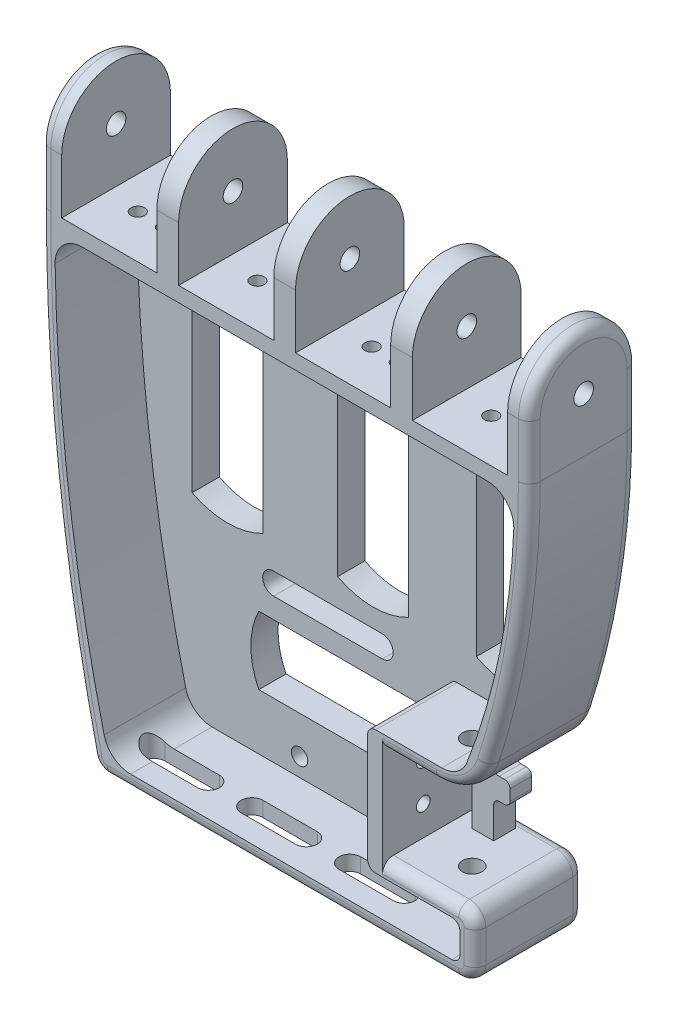
SolidWorks part; units mm, degrees
note: The reader was unsure of these and kept them because the rebuilt part matched: shared geometry of "Sketch4<4>".
ref_plane "Front Plane" through (0, 0, 0) normal (0, 0, 1) x (1, 0, 0)
ref_plane "Top Plane" through (0, 0, 0) normal (0, 1, 0) x (1, 0, 0)
ref_plane "Right Plane" through (0, 0, 0) normal (1, 0, 0) x (0, 0, -1)
sketch "Sketch1" plane through (0, 0, 0) normal (0, 0, 1) x (1, 0, 0)
  line L0 (0, 0) -> (-70, 0)
  line L1 (10, 85) -> (-80, 85)
  line L2 (0.003, 29.6) -> (-16.997, 29.6)
  line L3 (-16.997, 29.6) -> (-16.997, 12)
  line L5 (-16.997, 12) -> (0, 12)
  line L6 (0, 12) -> (0, 0)
  arc A0 (-80, 85) -> (-70, 0) centre (286.25, 85) ccw
  arc A1 (10, 85) -> (0.003, 29.6) centre (-148.5029, 85) cw
  point P5 (-35, 85)
  point P6 (-35, 0)
  dimension "D5" = 17.6
  dimension "D6" = 12
  dimension "D7" = 16.997
  dimension "D4" = 17
  dimension "D1" = 90
  dimension "D2" = 70
  dimension "D3" = 85
extrude "Boss-Extrude1" add sketch "Sketch1" along normal blind 20
sketch "Sketch2" plane through (0, 0, 20) normal (0, 0, 1) x (1, 0, 0)
  line L0 (-77.25, 82.25) -> (7.25, 82.25)
  line L1 (-2.7437, 32.35) -> (-19.7437, 32.35)
  line L2 (-19.7437, 32.35) -> (-19.7437, 9.5)
  line L3 (-19.7437, 9.5) -> (-2.75, 9.5)
  line L4 (-2.75, 9.5) -> (-2.75, 2.75)
  line L5 (-2.75, 2.75) -> (-67.25, 2.75)
  line L6 (0, 12) -> (-16.997, 12) construction
  arc A0 (7.25, 82.25) -> (-2.7437, 32.35) centre (-122.326, 82.25) cw
  arc A1 (-77.25, 82.25) -> (-67.25, 2.75) centre (243.7625, 82.25) ccw
  arc A2 (-72.2104, 82.25) -> (-77.2098, 77.1709) centre (-72.2104, 77.25) ccw
  arc A3 (7.1456, 77.0493) -> (2.1496, 82.25) centre (2.1496, 77.25) ccw
  arc A4 (-6.1229, 32.35) -> (-1.4589, 35.5479) centre (-6.1229, 37.35) ccw
  arc A5 (-68.2018, 6.5712) -> (-63.3428, 2.75) centre (-63.3428, 7.75) ccw
  arc A6 (-2.75, 8) -> (-4.25, 9.5) centre (-4.25, 8) ccw
  arc A7 (-4.25, 2.75) -> (-2.75, 4.25) centre (-4.25, 4.25) ccw
  arc A8 (-19.7437, 11) -> (-18.2437, 9.5) centre (-18.2437, 11) ccw
  arc A9 (-18.2437, 32.35) -> (-19.7437, 30.85) centre (-18.2437, 30.85) ccw
  point P10 (-35, 82.25)
  point P11 (-35, 2.75)
  dimension "D7" = 2.75
  dimension "D9" = 10
  dimension "D11" = 3
  dimension "D12" = 3
  dimension "D13" = 3
  dimension "D1" = 2.75
  dimension "D2" = 2.75
  dimension "D3" = 2.7467
  dimension "D4" = 2.7467
  dimension "D5" = 2.75
  dimension "D6" = 2.75
  dimension "D8" = 2.75
  dimension "D10" = 2.5
extrude "Cut-Extrude1" cut sketch "Sketch2" against normal blind 15 contours L5 A7 L4 A6 L3 L2 L1 A4 A0 A3 L0 A2 A1 A5 | A9 L1 L2 | A8 L2 L3
sketch "Sketch3" plane through (0, 85, 0) normal (0, 1, 0) x (1, 0, 0)
  line L0 (10, -20) -> (-80, -20) construction
  line L1 (-80, 0) -> (-76, 0)
  line L2 (-80, 0) -> (-80, -20)
  line L3 (-80, -20) -> (-76, -20)
  line L4 (-76, 0) -> (-76, -20)
  line L5 (-58.5, -20) -> (-54.5, -20)
  line L6 (-58.5, -20) -> (-58.5, 0)
  line L7 (-58.5, 0) -> (-54.5, 0)
  line L8 (-54.5, -20) -> (-54.5, 0)
  line L9 (10, 0) -> (-80, 0) construction
  line L10 (10, -20) -> (10, 0) construction
  line L11 (-37, 0) -> (-33, 0)
  line L12 (-37, -20) -> (-33, -20)
  line L13 (-37, 0) -> (-37, -20)
  line L15 (-15.5, 0) -> (-11.5, 0)
  line L16 (-15.5, 0) -> (-15.5, -20)
  line L17 (-15.5, -20) -> (-11.5, -20)
  line L18 (-11.5, 0) -> (-11.5, -20)
  line L19 (6, 0) -> (10, 0)
  line L20 (6, 0) -> (6, -20)
  line L21 (6, -20) -> (10, -20)
  line L22 (10, 0) -> (10, -20)
  line L23 (-33, 0) -> (-33, -20)
  point P27 (-58.5, -10)
  dimension "D1" = 4
  dimension "D2" = 4
  dimension "D3" = 4
  dimension "D4" = 4
  dimension "D5" = 4
  dimension "D6" = 17.5
  dimension "D7" = 17.5
  dimension "D8" = 17.5
extrude "Boss-Extrude2" add sketch "Sketch3" along normal blind 20
sketch "Sketch4" plane through (-80, 0, 0) normal (-1, 0, 0) x (0, 0, 1)
  line L0 (0, 85) -> (0, 105)
  line L1 (0, 105) -> (20, 105)
  line L2 (0, 85) -> (20, 85)
  line L3 (0, 95) -> (8.2, 95)
  line L4 (11.8, 95) -> (20, 95)
  line L5 (20, 105) -> (20, 85)
  arc A0 (0, 95) -> (20, 95) centre (10, 95) cw
  circle A1 centre (10, 95) radius 1.8
  point P3 (0, 95)
  point P5 (10, 105)
  dimension "D1" = 3.6
extrude "Cut-Extrude2" cut sketch "Sketch4" against normal through all
extrude "Cut-Extrude3" cut sketch "Sketch4<4>" against normal through all contours A1
sketch "Sketch4<4>" plane through (-80, 0, 0) normal (-1, 0, 0) x (0, 0, 1) same geometry as "Sketch4"
ref_plane "Plane1" through (0, 85, 0) normal (0, 1, 0) x (1, 0, 0)
sketch "Sketch7" plane through (0, 32.35, 0) normal (0, 1, 0) x (1, 0, 0)
  line L4 (-18.2437, -5) -> (-18.2437, -20) construction
  line L6 (0.003, -20) -> (0.003, 0) construction
  circle A0 centre (-7.997, -12.5) radius 1.8
  point P10 (-18.2437, -12.5)
  dimension "D1" = 3.6
  dimension "D2" = 8
extrude "Cut-Extrude5" cut sketch "Sketch7" against normal blind 25
sketch "Sketch9" plane through (0, 85, 0) normal (0, 1, 0) x (1, 0, 0)
  line L0 (-76, -20) -> (-76, -10) construction
  line L2 (-56.5, 0) -> (-56.5, -50000) construction
  line L3 (-54.5, 0) -> (-58.5, 0) construction
  line L4 (-35, 0) -> (-35, -50000) construction
  line L5 (-33, 0) -> (-37, 0) construction
  line L7 (-58.5, 0) -> (-76, 0) construction
  circle A0 centre (-70, -12) radius 1.25
  circle A1 centre (-65, -12) radius 1.25
  circle A2 centre (-48, -12) radius 1.25
  circle A3 centre (-43, -12) radius 1.25
  circle A4 centre (-27, -12) radius 1.25
  circle A5 centre (-22, -12) radius 1.25
  circle A6 centre (-5, -12) radius 1.25
  circle A7 centre (0, -12) radius 1.25
  point P14 (-56.5, 0)
  point P22 (-35, 0)
  point P34 (-76, -15)
  dimension "D1" = 2.5
  dimension "D2" = 2.5
  dimension "D3" = 12
  dimension "D4" = 6
  dimension "D5" = 5
extrude "Cut-Extrude6" cut sketch "Sketch9" against normal blind 10
sketch "Sketch10" plane through (0, 0, 6) normal (0, 0, 1) x (1, 0, 0)
  line L0 (-35.4209, 73.25) -> (35.4209, 73.25) construction
  line L1 (-32.0539, 38.25) -> (49967.9461, 38.25) construction
  line L2 (2.1496, 82.25) -> (-72.2104, 82.25) construction
  line L4 (-67, 73.25) -> (-54, 73.25)
  line L5 (-67, 73.25) -> (-67, 38.25)
  line L6 (-67, 38.25) -> (-54, 38.25)
  line L7 (-54, 73.25) -> (-54, 38.25)
  line L8 (-40.25, 73.25) -> (-27.25, 73.25)
  line L9 (-40.25, 73.25) -> (-40.25, 38.25)
  line L10 (-40.25, 38.25) -> (-27.25, 38.25)
  line L11 (-27.25, 73.25) -> (-27.25, 38.25)
  line L12 (-14.75, 73.25) -> (-1.75, 73.25)
  line L13 (-14.75, 73.25) -> (-14.75, 38.25)
  line L14 (-14.75, 38.25) -> (-1.75, 38.25)
  line L15 (-1.75, 73.25) -> (-1.75, 38.25)
  line L16 (6, 85) -> (-11.5, 85) construction
  line L19 (-15.5, 85) -> (-33, 85) construction
  arc A0 (-67, 73.25) -> (-54, 73.25) centre (-60.5, 60.8504) cw
  arc A1 (-67, 38.25) -> (-54, 38.25) centre (-60.5, 50.6496) ccw
  arc A2 (-40.25, 73.25) -> (-27.25, 73.25) centre (-33.75, 60.8504) cw
  arc A3 (-40.25, 38.25) -> (-27.25, 38.25) centre (-33.75, 50.6496) ccw
  arc A4 (-14.75, 38.25) -> (-1.75, 38.25) centre (-8.25, 50.6496) ccw
  arc A5 (-14.75, 73.25) -> (-1.75, 73.25) centre (-8.25, 60.8504) cw
  point P6 (0, 73.25)
  point P21 (-2.75, 85)
  point P25 (-24.25, 85)
  dimension "D9" = 14
  dimension "D1" = 9
  dimension "D2" = 35
  dimension "D3" = 13
  dimension "D4" = 13
  dimension "D5" = 13
  dimension "D6" = 12
  dimension "D7" = 16
  dimension "D8" = 13
extrude "Cut-Extrude9" cut sketch "Sketch10" against normal mid plane 43 contours L7 L4 L5 L6 | L11 L8 L9 L10 | L15 L12 L13 L14 | L14 A4 | L10 A3 | L6 A1 | A0 L4 | A2 L8 | A5 L12
sketch "Sketch11" plane through (-19.7437, 0, 0) normal (-1, 0, 0) x (0, 0, 1)
  line L1 (6, 32.35) -> (16, 32.35) construction
  line L2 (5, 30.85) -> (20, 30.85) construction
  circle A0 centre (12.5, 24.455) radius 1.25
  circle A1 centre (12.5, 17.455) radius 1.25
  point P12 (12.5, 30.85)
  dimension "D1" = 2.5
  dimension "D2" = 2.5
  dimension "D3" = 7
  dimension "D4" = 7.895
extrude "Cut-Extrude10" cut sketch "Sketch11" against normal blind 33
sketch "Sketch12" plane through (0, 0, 6) normal (0, 0, 1) x (1, 0, 0)
  line L1 (-54.7437, 25.5) -> (-24.7437, 25.5)
  line L2 (-54.7437, 25.5) -> (-54.7437, 13)
  line L3 (-54.7437, 13) -> (-24.7437, 13)
  line L4 (-24.7437, 25.5) -> (-24.7437, 13)
  line L6 (-19.7437, 9.5573) -> (-19.7437, 32.35) construction
  arc A0 (-54.7437, 25.5) -> (-54.7437, 13) centre (-42.2162, 19.25) ccw
  arc A1 (-24.7437, 25.5) -> (-24.7437, 13) centre (-37.2712, 19.25) cw
  dimension "D5" = 14
  dimension "D6" = 14
  dimension "D1" = 30
  dimension "D2" = 12.5
  dimension "D3" = 5
  dimension "D4" = 13
extrude "Cut-Extrude11" cut sketch "Sketch12" against normal mid plane 63 contours L4 L1 L2 L3 | A1 L4 | L2 A0
sketch "Sketch15" plane through (0, 0, 6) normal (0, 0, 1) x (1, 0, 0)
  line L0 (-68, 73.25) -> (-68, 43.25) construction
  line L1 (-2.75, 4.25) -> (-2.75, 8) construction
  circle A0 centre (-47.25, 6.125) radius 1.5
  circle A1 centre (-19.7437, 6.125) radius 1.5
  circle A2 centre (1.75, 76.125) radius 1.5
  circle A3 centre (-47.25, 76.125) radius 1.5
  point P22 (-2.75, 6.125)
  dimension "D1" = 3
  dimension "D4" = 49
  dimension "D5" = 70
  dimension "D6" = 20.75
extrude "Cut-Extrude13" cut sketch "Sketch15" along normal mid plane 100
sketch "Sketch16" plane through (0, 0, 0) normal (0, -1, 0) x (1, 0, 0)
  line L0 (-37, 14) -> (-47, 14) construction
  line L1 (-37, 12) -> (-47, 12)
  line L2 (-37, 16) -> (-47, 16)
  line L3 (-29, 14) -> (-19, 14) construction
  line L4 (-29, 16) -> (-19, 16)
  line L5 (-29, 12) -> (-19, 12)
  line L6 (-55, 14) -> (-65, 14) construction
  line L7 (-55, 12) -> (-65, 12)
  line L8 (-55, 16) -> (-65, 16)
  line L9 (-70, 20) -> (0, 20) construction
  arc A0 (-37, 12) -> (-37, 16) centre (-37, 14) ccw
  arc A1 (-47, 16) -> (-47, 12) centre (-47, 14) ccw
  arc A2 (-29, 16) -> (-29, 12) centre (-29, 14) ccw
  arc A3 (-19, 12) -> (-19, 16) centre (-19, 14) ccw
  arc A4 (-55, 12) -> (-55, 16) centre (-55, 14) ccw
  arc A5 (-65, 16) -> (-65, 12) centre (-65, 14) ccw
  point P2 (-42, 14)
  point P7 (-24, 14)
  point P14 (-60, 14)
  dimension "D1" = 2
  dimension "D2" = 10
  dimension "D3" = 55
  dimension "D4" = 18
  dimension "D5" = 18
  dimension "D6" = 6
extrude "Cut-Extrude14" cut sketch "Sketch16" against normal blind 7
sketch "Sketch17" plane through (0, 0, 6) normal (0, 0, 1) x (1, 0, 0)
  line L0 (-52.0304, 31.25) -> (-32.0304, 31.25) construction
  line L1 (-52.0304, 33.25) -> (-32.0304, 33.25)
  line L2 (-52.0304, 29.25) -> (-32.0304, 29.25)
  line L3 (2.1496, 82.25) -> (-72.2104, 82.25) construction
  line L4 (7.25, 82.25) -> (-77.25, 82.25) construction
  arc A0 (-52.0304, 33.25) -> (-52.0304, 29.25) centre (-52.0304, 31.25) ccw
  arc A1 (-32.0304, 29.25) -> (-32.0304, 33.25) centre (-32.0304, 31.25) ccw
  arc A2 (-52.0304, 33.25) -> (-50.0304, 31.25) centre (-52.0304, 31.25) ccw
  arc A3 (-34.0304, 31.25) -> (-32.0304, 33.25) centre (-32.0304, 31.25) ccw
  arc A4 (-44.0304, 31.25) -> (-40.0304, 31.25) centre (-42.0304, 31.25) ccw
  point P2 (-42.0304, 31.25)
  point P7 (-30.0304, 31.25)
  point P11 (-35.0304, 82.25)
  dimension "D1" = 20
  dimension "D2" = 2
  dimension "D3" = 7
  dimension "D4" = 51
extrude "Cut-Extrude15" cut sketch "Sketch17" against normal mid plane 57
fillet "Fillet1" radius 10 1 edges at (0.003, 29.6, 10)
fillet "Fillet2" radius 3 1 edges at (0, 12, 10)
fillet "Fillet3" radius 3 1 edges at (0, 0, 10)
fillet "Fillet4" radius 3 1 edges at (-70, 0, 10)
fillet "Fillet6" radius 2 9 edges at (-12.0535, 29.6, 0) (-12.0535, 29.6, 20) (-1.2181, 31.52, 0) (-1.2181, 31.52, 20) (10, 90, 0) (10, 90, 20) (8.0913, 60.4761, 20) (8.0913, 60.4761, 0) (10, 105, 10)
fillet "Fillet7" radius 2 17 edges at (-9.9985, 12, 20) (-9.9985, 12, 0) (-0.8787, 11.1213, 20) (-0.8787, 11.1213, 0) (0, 6, 20) (0, 6, 0) (-0.8787, 0.8787, 20) (-0.8787, 0.8787, 0) (-35.3118, 0, 20) (-35.3118, 0, 0) (-69.4902, 0.6514, 20) (-69.4902, 0.6514, 0) (-80, 90, 20) (-80, 90, 0) (-77.6289, 43.392, 0) (-77.6289, 43.392, 20) (-80, 105, 10)
sketch "Sketch18" plane through (0, 29.6, 0) normal (0, -1, 0) x (1, 0, 0)
  line L1 (-14.0535, 6.5) -> (-10.0535, 6.5)
  line L2 (-14.0535, 6.5) -> (-14.0535, 2.5)
  line L3 (-14.0535, 2.5) -> (-10.0535, 2.5)
  line L4 (-10.0535, 6.5) -> (-10.0535, 2.5)
  line L5 (-16.997, 2) -> (-7.11, 2) construction
  point P4 (-12.0535, 6.5)
  point P7 (-12.0535, 2)
  dimension "D1" = 4
  dimension "D2" = 4
  dimension "D3" = 0.5
extrude "Boss-Extrude3" add sketch "Sketch18" along normal up to surface (17.6 mm away) up to face at (-7.997, 12, 10.7)
sketch "Sketch19" plane through (-10.0535, 0, 0) normal (1, 0, 0) x (0, 0, -1)
  line L0 (-6.5, 12) -> (-6.5, 29.6) construction
  line L1 (-6.5, 22.8) -> (-2.5, 22.8)
  line L2 (-6.5, 22.8) -> (-6.5, 18.8)
  line L3 (-6.5, 18.8) -> (-2.5, 18.8)
  line L4 (-2.5, 22.8) -> (-2.5, 18.8)
  line L5 (-2.5, 12) -> (-2.5, 29.6) construction
  line L6 (0, 10) -> (0, 31.6) construction
  point P8 (-2.5, 20.8)
  point P11 (0, 20.8)
  dimension "D1" = 4
extrude "Boss-Extrude4" add sketch "Sketch19" along normal blind 3
fillet "Fillet12" radius 1 4 edges at (-10.0535, 18.8, 4.5) (-10.0535, 22.8, 4.5) (-7.0535, 18.8, 4.5) (-7.0535, 22.8, 4.5)
